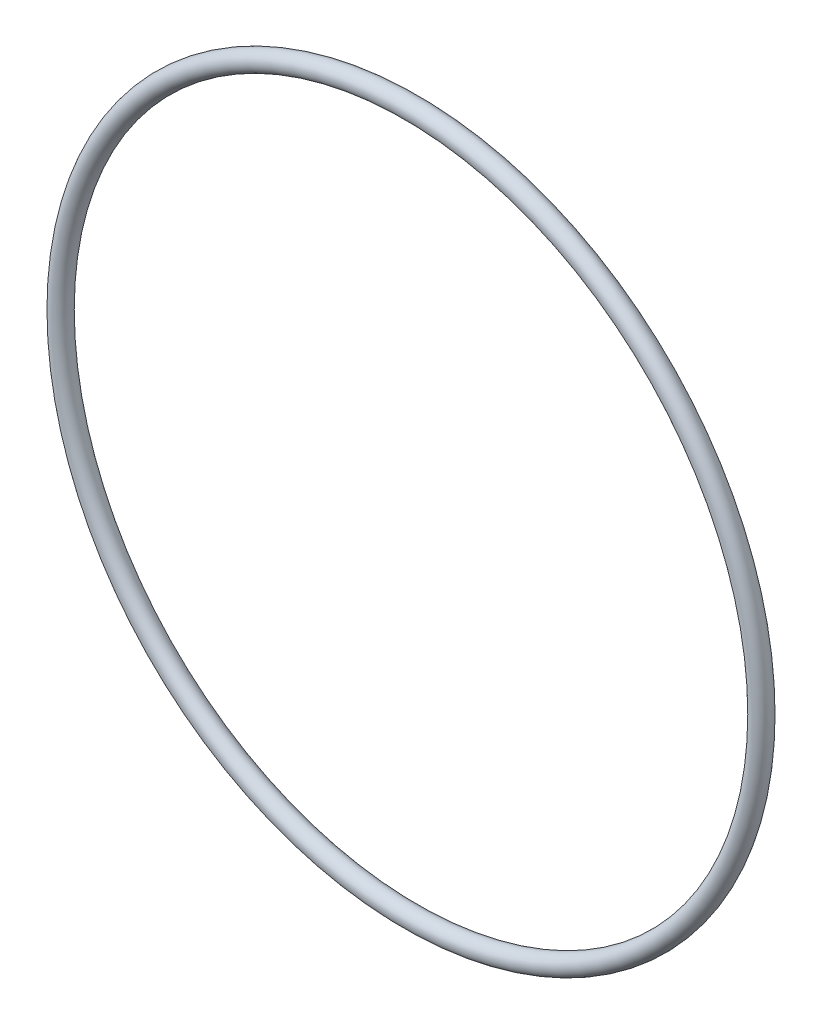
SolidWorks part; units mm, degrees
ref_plane "Front" through (0, 0, 0) normal (0, 0, 1) x (1, 0, 0)
ref_plane "Top" through (0, 0, 0) normal (0, 1, 0) x (1, 0, 0)
ref_plane "Right" through (0, 0, 0) normal (1, 0, 0) x (0, 0, -1)
sketch "Sketch1" plane through (0, 0, 0) normal (0, 0, 1) x (1, 0, 0)
  circle A0 centre (0, 0) radius 54.7
  dimension "d1" = 109.4
sketch "Sketch2" plane through (0, 0, 0) normal (0, 1, 0) x (1, 0, 0)
  circle A0 centre (-56.25, 0) radius 1.55
  point P2 (-54.7, 0)
  dimension "d2" = 3.1
sweep "Sweep1" add profiles "Sketch2" path "Sketch1"
ref_axis "Axis1" through (0, 0, -4.8575) along (0, 0, 1)
